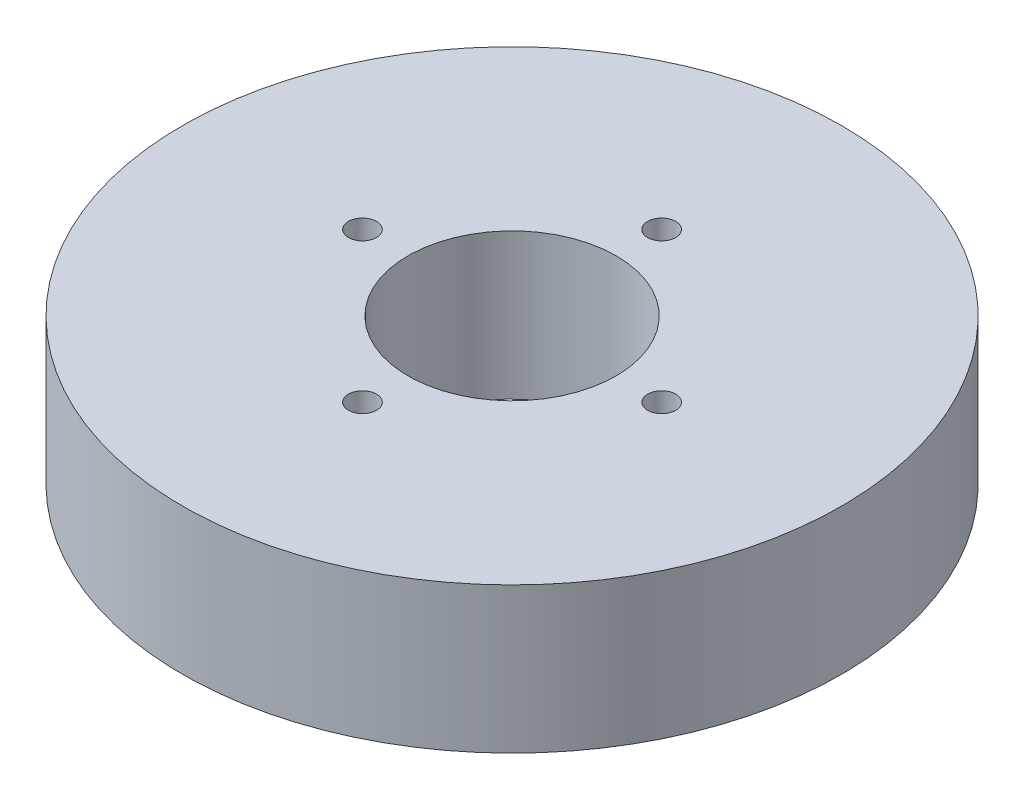
SolidWorks part; units mm, degrees
ref_plane "Front Plane" through (0, 0, 0) normal (0, 0, 1) x (1, 0, 0)
ref_plane "Top Plane" through (0, 0, 0) normal (0, 1, 0) x (1, 0, 0)
ref_plane "Right Plane" through (0, 0, 0) normal (1, 0, 0) x (0, 0, -1)
sketch "Sketch1" plane through (0, 0, 0) normal (0, 1, 0) x (1, 0, 0)
  circle A0 centre (0, 0) radius 47.5
  dimension "FLANGE_OD" = 95
extrude "Boss-Extrude1" add sketch "Sketch1" along normal blind 21
sketch "Sketch2" plane through (0, 0, 0) normal (0, 1, 0) x (1, 0, 0)
  circle A0 centre (0, 0) radius 15
  dimension "BORE_D" = 30
extrude "Cut-Extrude1" cut sketch "Sketch2" along normal through all
sketch "Sketch3" plane through (0, 21, 0) normal (0, 1, 0) x (1, 0, 0)
  circle A0 centre (0, 0) radius 21.5611 construction
  circle A1 centre (-21.5611, 0) radius 2.0226
  dimension "BOLT_D" = 4.0453
  dimension "BOLT_PCD" = 43.1223
extrude "Cut-Extrude2" cut sketch "Sketch3" against normal blind 19.2145
pattern_circular "CirPattern1" count 4 over 360 about axis through (0, 0, 0) along (0, 1, 0) of "Cut-Extrude2"
